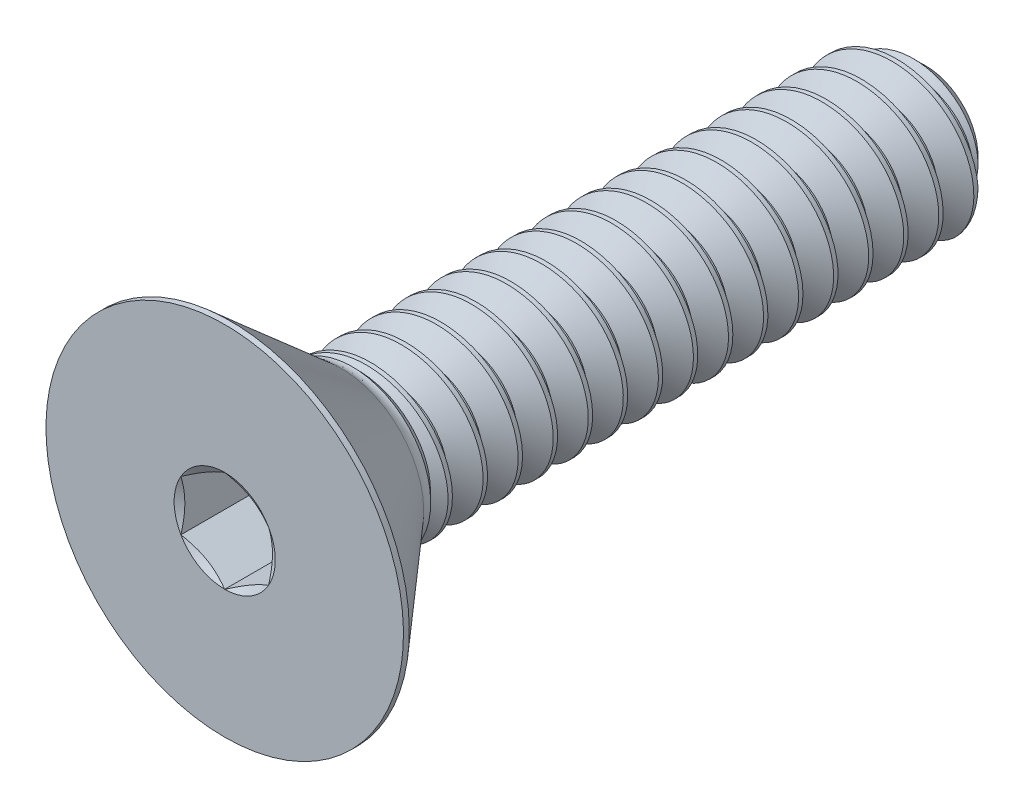
SolidWorks part; units mm, degrees
material "Alloy Steel"
ref_plane "Front" through (0, 0, 0) normal (0, 0, 1) x (1, 0, 0)
ref_plane "Top" through (0, 0, 0) normal (0, 1, 0) x (1, 0, 0)
ref_plane "Right" through (0, 0, 0) normal (1, 0, 0) x (0, 0, -1)
sketch "Sketch1" plane through (0, 0, 0) normal (1, 0, 0) x (0, 0, -1)
  line L0 (0, 3.2385) -> (0.1054, 3.2385) construction
  line L1 (0.1054, 3.2385) -> (2.1082, 1.4975) construction
  line L2 (0, 1.4224) -> (12.7, 1.4224)
  line L3 (12.7, 1.4224) -> (12.7, 0)
  line L4 (12.7, 0) -> (0, 0)
  line L5 (0, 0) -> (0, 3.2385) construction
  line L6 (0, 3.2385) -> (0, -3.2385) construction
  line L7 (12.7, 1.4224) -> (12.7, -1.4224) construction
  line L8 (0, -3.2385) -> (0.1054, -3.2385) construction
  line L9 (0.1054, -3.2385) -> (2.1082, -1.4975) construction
  line L11 (0, 1.4224) -> (0, 0)
  line L12 (2.3091, 1.4224) -> (2.3091, 0) construction
  line L13 (-12.7, 0) -> (-12.7, 1.4224) construction
  arc A1 (2.1082, 1.4975) -> (2.3091, 1.4224) centre (2.3091, 1.7286) ccw construction
  dimension "D1" = 0.1054
  dimension "Head Ht" = 2.1082
  dimension "Head Dia" = 6.477
  dimension "Dia" = 2.8448
  dimension "Lg" = 12.7
  dimension "Head Angle" = 82
  dimension "Min Thread" = 25.4
revolve "Revolve1" add sketch "Sketch1" angle 360 mid plane about L4
sketch "Sketch3" plane through (0, 0, -12.7) normal (0, 0, -1) x (-1, 0, 0)
  circle A0 centre (0, 0) radius 1.4224
curve "Helix/Spiral1" pitch 0.635 height 12.7 radius 1.4224 centre (0, 0, -12.7) axis (0, 0, 1) start towards (0, 1, 0)
sketch "Sketch2" plane through (0, 0, 0) normal (1, 0, 0) x (0, 0, -1)
  line L0 (12.7, 1.4224) -> (13.2556, 1.4224)
  line L1 (13.2556, 1.4224) -> (13.0175, 1.01)
  line L2 (13.0175, 1.01) -> (12.9381, 1.01)
  line L3 (12.9381, 1.01) -> (12.7, 1.4224)
  line L4 (12.8191, 1.2162) -> (13.1366, 1.2162) construction
  dimension "D1" = 60
  dimension "D2" = 0.0794
  dimension "D3" = 0.3175
ref_plane "Plane2" through (0, 0, 12.7) normal (0, 0, 1) x (1, 0, 0)
chamfer "Chamfer1" distance 0.4763 angle 45 1 edges at (0, 1.4224, -12.7)
sweep "Cut-Sweep1" cut profiles "Sketch2" path "Helix/Spiral1"
sketch "Sketch7" plane through (0, 0, 0) normal (1, 0, 0) x (0, 0, -1)
  line L0 (0, 3.2385) -> (0.1054, 3.2385) construction
  line L1 (0.1054, 3.2385) -> (2.1082, 1.4975) construction
  line L2 (0, 3.2385) -> (0.1054, 3.2385)
  line L3 (0.1054, 3.2385) -> (2.1082, 1.4975)
  line L4 (2.3091, 1.4224) -> (2.3091, 0) construction
  line L5 (2.3091, 1.4224) -> (2.3091, 0)
  line L7 (0, 0) -> (0, 3.2385) construction
  line L8 (0, 0) -> (0, 3.2385)
  line L9 (0, 0) -> (2.3091, 0)
  line L10 (5.7417, 0) -> (-5.7417, 0) construction
  arc A0 (2.1082, 1.4975) -> (2.3091, 1.4224) centre (2.3091, 1.7286) ccw construction
  arc A1 (2.1082, 1.4975) -> (2.3091, 1.4224) centre (2.3091, 1.7286) ccw
revolve "Revolve2" add sketch "Sketch7" angle 360 mid plane about L9
ref_plane "Plane1" through (0, 0, -2.3091) normal (0, 0, 1) x (1, 0, 0)
sketch "Sketch8" plane through (0, 0, -2.3091) normal (0, 0, 1) x (1, 0, 0)
  circle A0 centre (0, 0) radius 1.4224
extrude "Boss-Extrude1" add sketch "Sketch8" against normal through all draft 46
sketch "Sketch5" plane through (0, 0, 0) normal (0, 0, 1) x (1, 0, 0)
  line L0 (0, 0) -> (-0.9165, 0) construction
  line L1 (0, 0) -> (-2.7496, 1.5875) construction
  line L2 (0, 0) -> (-2.7496, -1.5875) construction
  line L6 (0, 0.9165) -> (0, 0.7559) construction
  line L7 (0, 0.7559) -> (0, 0.5953) construction
  line L9 (0, 0.9165) -> (-0.7937, 0.4583)
  line L10 (-0.7937, 0.4583) -> (-0.7937, -0.4583)
  line L11 (-0.7937, -0.4583) -> (0, -0.9165)
  line L12 (0, -0.9165) -> (0.7937, -0.4583)
  line L13 (0.7937, -0.4583) -> (0.7938, 0.4583)
  line L14 (0.7938, 0.4583) -> (0, 0.9165)
  circle A0 centre (0, 0) radius 0.9165 construction
  circle A1 centre (0, 0) radius 0.7559 construction
  circle A2 centre (0, 0) radius 0.5953 construction
  circle A3 centre (0, 0) radius 0.7938 construction
  dimension "D3" = 1.1906
  dimension "Hex" = 1.5875
  dimension "D4" = 30
  dimension "D5" = 30
extrude "Cut-Extrude2" cut sketch "Sketch5" against normal blind 1.4757
sketch "Sketch6" plane through (0, 0, 0) normal (0, 0, 1) x (1, 0, 0)
  circle A0 centre (0, 0) radius 0.9165
extrude "Cut-Extrude3" cut sketch "Sketch6" against normal blind 1.4757 draft 60
sketch "Sketch9" [suppressed] plane through (0, 0, -3.6076) normal (0, 0, 1) x (1, 0, 0)
  circle A1 centre (0, 0) radius 2.413
  circle A2 centre (0, 0) radius 2.413
  point P0 (0, 2.413)
  dimension "D1" = 0
extrude "Boss-Extrude2" [suppressed] add sketch "Sketch9" against normal up to surface (15.4424 mm away) up to plane "Plane2"
sketch "Sketch10" plane through (0, 0, 0) normal (1, 0, 0) x (0, 0, -1)
  line L0 (12.7, 1.4224) -> (12.7, -1.4224) construction
  point P0 (11.7475, -1.4224)
  dimension "D1" = 0.9525
equation "\"D3@Helix/Spiral1\" = \"Lg@Sketch1\""
equation "\"D2@Sketch2\" = \"D4@Helix/Spiral1\" * .125"
equation "\"D3@Sketch2\" = \"D4@Helix/Spiral1\" * .5"
equation "\"D1@Chamfer1\" = \"D4@Helix/Spiral1\" * .75"
equation "\"D1@Cut-Extrude2\" = \"Head Ht@Sketch1\" * .7"
equation "\"D1@Sketch1\" = \"Head Ht@Sketch1\" * .05"
equation "\"D1@Sketch10\" = \"D4@Helix/Spiral1\" * 1.5"
equation "\"D1@Cut-Extrude3\" = \"D1@Cut-Extrude2\""
equation "\"D3@Sketch5\" = \"Hex@Sketch5\" * .75"
